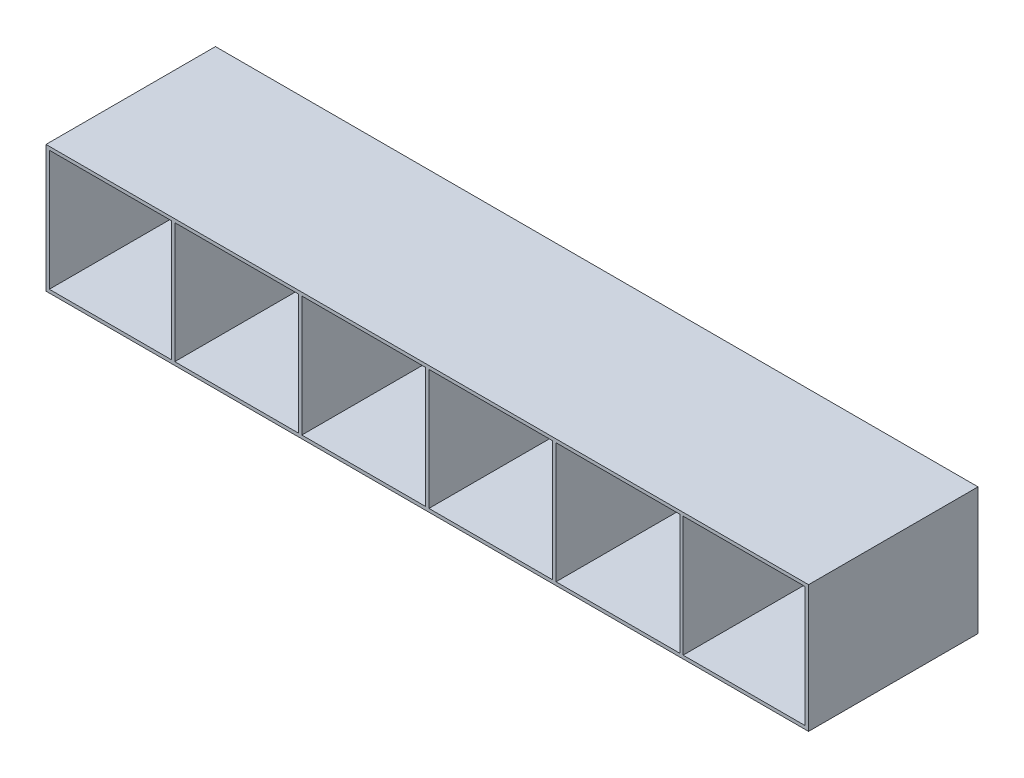
SolidWorks part; units mm, degrees
ref_plane "Спереди" through (0, 0, 0) normal (0, 0, 1) x (1, 0, 0)
ref_plane "Сверху" through (0, 0, 0) normal (0, 1, 0) x (1, 0, 0)
ref_plane "Справа" through (0, 0, 0) normal (1, 0, 0) x (0, 0, -1)
sketch "Эскиз1" plane through (0, 0, 0) normal (0, 0, 1) x (1, 0, 0)
  line L0 (-226.6, 36.1) -> (-226.6, -36.1)
  line L1 (-228.6, 38.1) -> (228.6, 38.1)
  line L2 (-228.6, 38.1) -> (-228.6, -38.1)
  line L3 (-228.6, -38.1) -> (228.6, -38.1)
  line L4 (228.6, 38.1) -> (228.6, -38.1)
  line L5 (-228.6, 38.1) -> (228.6, -38.1) construction
  line L6 (-228.6, -38.1) -> (228.6, 38.1) construction
  line L7 (-226.6, -36.1) -> (226.6, -36.1)
  line L8 (226.6, 36.1) -> (226.6, -36.1)
  line L9 (-226.6, 36.1) -> (226.6, 36.1)
  line L10 (-77.2, 38.1) -> (-77.2, -38.1)
  line L11 (-151.4, 38.1) -> (-153.4, 38.1)
  line L12 (-151.4, 38.1) -> (-151.4, -38.1)
  line L13 (-151.4, -38.1) -> (-153.4, -38.1)
  line L14 (-153.4, 38.1) -> (-153.4, -38.1)
  line L15 (-151.4, 38.1) -> (-153.4, -38.1) construction
  line L16 (-151.4, -38.1) -> (-153.4, 38.1) construction
  line L17 (-75.2, -38.1) -> (-77.2, -38.1)
  line L18 (-75.2, 38.1) -> (-75.2, -38.1)
  line L19 (-75.2, 38.1) -> (-77.2, 38.1)
  line L20 (-1, 38.1) -> (-1, -38.1)
  line L21 (1, -38.1) -> (-1, -38.1)
  line L22 (1, 38.1) -> (1, -38.1)
  line L23 (1, 38.1) -> (-1, 38.1)
  line L24 (75.2, 38.1) -> (75.2, -38.1)
  line L25 (77.2, -38.1) -> (75.2, -38.1)
  line L26 (77.2, 38.1) -> (77.2, -38.1)
  line L27 (77.2, 38.1) -> (75.2, 38.1)
  line L28 (151.4, 38.1) -> (151.4, -38.1)
  line L29 (153.4, -38.1) -> (151.4, -38.1)
  line L30 (153.4, 38.1) -> (153.4, -38.1)
  line L31 (153.4, 38.1) -> (151.4, 38.1)
  point P0 (0, 0)
  point P10 (-152.4, 0)
  dimension "D1" = 457.2
  dimension "D2" = 76.2
  dimension "D4" = 2
  dimension "D3" = 2
  dimension "D5" = 5
extrude "Бобышка-Вытянуть1" add sketch "Эскиз1" along normal blind 101.6 contours L1 L4 L3 L2
extrude "Вырез-Вытянуть1" cut sketch "Эскиз1<3>" along normal through all contours L14 L9 L0 L7 | L9 L12 L7 L10 | L20 L9 L18 L7 | L24 L9 L22 L7 | L9 L26 L7 L8 | L28 L9 L26 L7 region at (-190, 0, 0) region at (-114.3, 0, 0) region at (-38.1, 0, 0) region at (38.1, 0, 0) region at (114.3, 0, 0) region at (190, 0, 0)
sketch "Эскиз1<3>" plane through (0, 0, 0) normal (0, 0, 1) x (1, 0, 0) same geometry as "Эскиз1"
